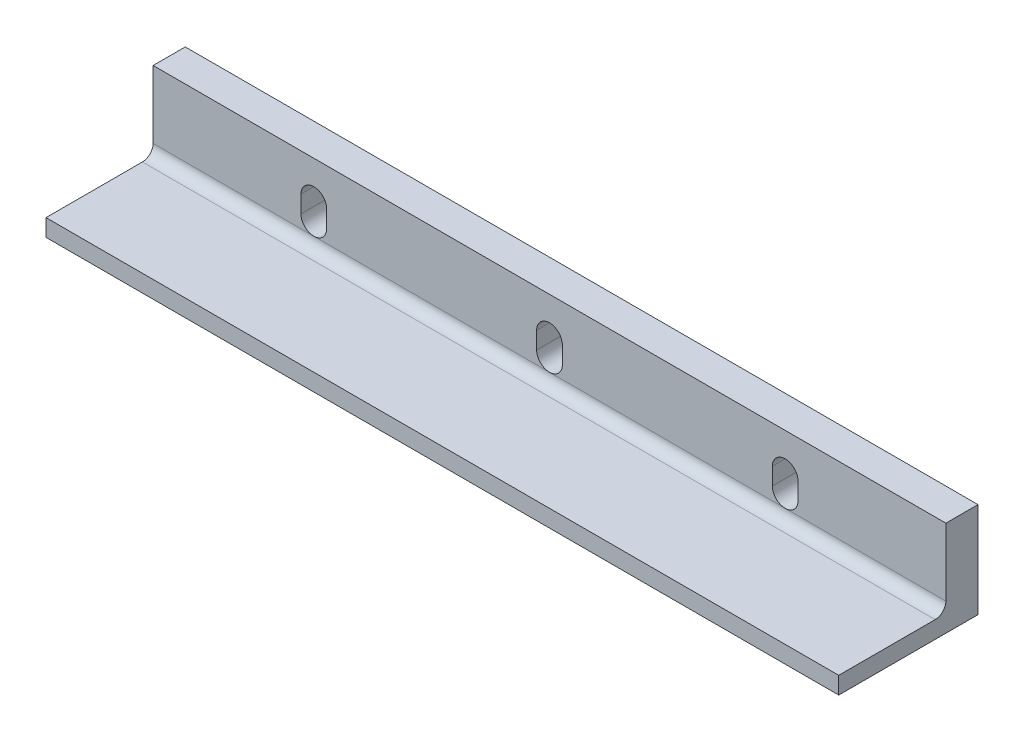
SolidWorks part; units mm, degrees
material "FR4_stuffedProtoboard"
ref_plane "Front Plane" through (0, 0, 0) normal (0, 0, 1) x (1, 0, 0)
ref_plane "Top Plane" through (0, 0, 0) normal (0, 1, 0) x (1, 0, 0)
ref_plane "Right Plane" through (0, 0, 0) normal (1, 0, 0) x (0, 0, -1)
sketch "Sketch1" plane through (0, 0, 0) normal (0, 1, 0) x (1, 0, 0)
  line L1 (-37, -6.5) -> (37, -6.5)
  line L2 (-37, -6.5) -> (-37, 6.5)
  line L3 (-37, 6.5) -> (37, 6.5)
  line L4 (37, -6.5) -> (37, 6.5)
  line L5 (-37, -6.5) -> (37, 6.5) construction
  line L6 (-37, 6.5) -> (37, -6.5) construction
  point P0 (0, 0)
  dimension "D1" = 13
  dimension "D2" = 74
extrude "Boss-Extrude1" add sketch "Sketch1" along normal blind 1.6
sketch "Sketch2" plane through (0, 1.6, 0) normal (0, 1, 0) x (1, 0, 0)
  line L0 (37, -6.5) -> (37, 6.5) construction
  line L1 (-37, 6.5) -> (37, 6.5)
  line L2 (-37, 6.5) -> (-37, 3.5)
  line L3 (-37, 3.5) -> (37, 3.5)
  line L4 (37, 6.5) -> (37, 3.5)
  dimension "D1" = 3
extrude "Boss-Extrude2" add sketch "Sketch2" along normal blind 7.3
fillet "Fillet1" radius 1 1 edges at (0, 1.6, -3.5)
sketch "Sketch3" plane through (0, 0, -6.5) normal (0, 0, 1) x (1, 0, 0)
  line L0 (0, 0) -> (0, 4.6) construction
  line L1 (22, 4.6) -> (-22, 4.6) construction
  point P6 (0, 4.6)
  dimension "D1" = 4.6
  dimension "D2" = 44
hole_wizard "M2 Clearance Slot1" positions "Sketch7" profile "Sketch8" size "M2" standard "ANSI Metric" slot yes end condition through all
sketch "Sketch7" plane through (0, 0, -3.5) normal (0, 0, 1) x (1, 0, 0)
  line L0 (-22, 2.6) -> (-22, 6.6) construction
  point P14 (-22, 4.6)
  point P19 (0, 4.6)
  point P22 (22, 4.6)
  dimension "D1" = 4
sketch "Sketch8" plane through (-22, 4.6, -3.5) normal (1, 0, 0) x (0, -1, 0)
  line L0 (0, 0) -> (0, 3)
  line L1 (0, 3) -> (1.2, 3)
  line L2 (1.2, 3) -> (1.2, 0)
  line L5 (1.2, 0) -> (0, 0)
  line L11 (0, -6.35) -> (0, 107.95) construction
  dimension "Thru Hole Dia." = 2.4
  dimension "Thru Hole Depth" = 3
